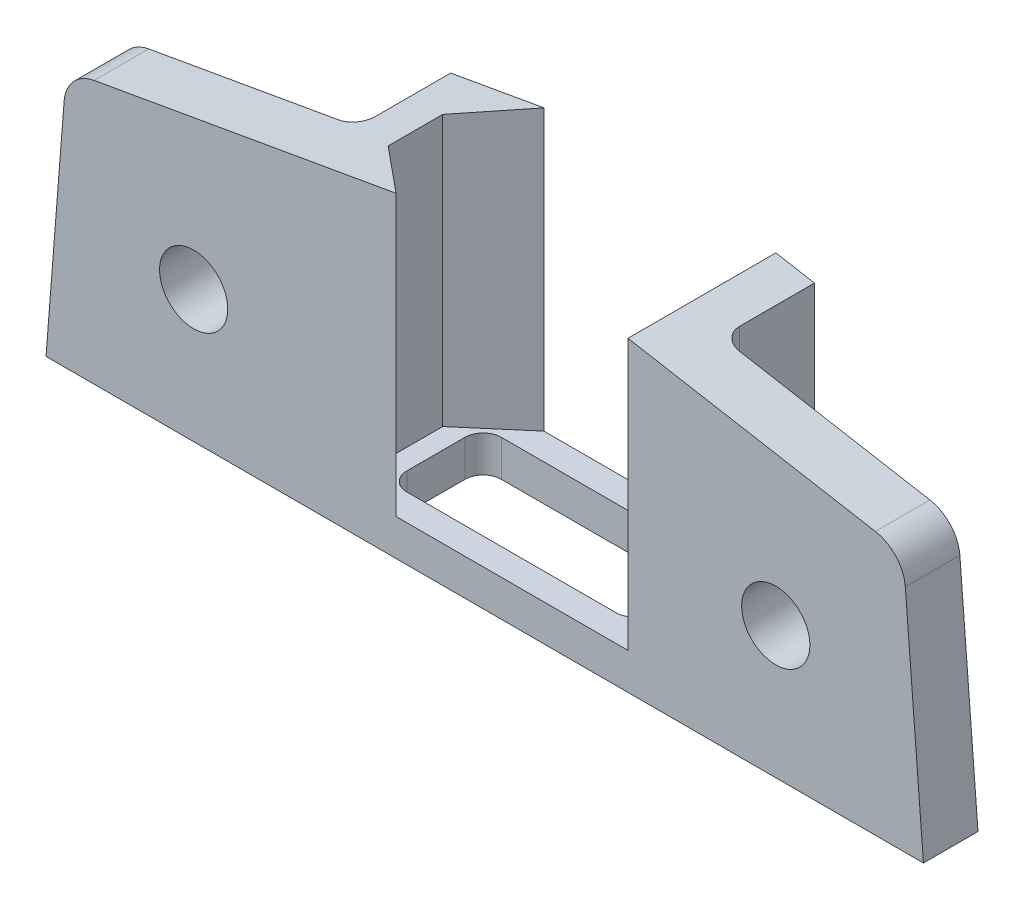
SolidWorks part; units mm, degrees
ref_plane "Front Plane" through (0, 0, 0) normal (0, 0, 1) x (1, 0, 0)
ref_plane "Top Plane" through (0, 0, 0) normal (0, 1, 0) x (1, 0, 0)
ref_plane "Right Plane" through (0, 0, 0) normal (1, 0, 0) x (0, 0, -1)
sketch "Sketch1" plane through (0, 0, 0) normal (0, 0, 1) x (1, 0, 0)
  line L0 (-24.457, 69.4319) -> (24.457, 69.4319)
  line L18 (24.457, 69.4319) -> (23.1215, 86.4007)
  line L19 (21.475, 88.2134) -> (0, 92)
  line L20 (0, 92) -> (-21.475, 88.2134)
  line L21 (-23.1215, 86.4007) -> (-24.457, 69.4319)
  line L22 (-24.5714, 68.9048) -> (-33.6515, 43.9576)
  line L23 (-33.4302, 42.1552) -> (-25.3419, 30.1639)
  line L24 (-25, 29.0455) -> (-25, -29.0455)
  line L25 (-25.3419, -30.1639) -> (-33.4302, -42.1552)
  line L26 (-33.6515, -43.9576) -> (-24.5714, -68.9048)
  line L27 (-24.457, -69.4319) -> (-23.1215, -86.4007)
  line L28 (-21.475, -88.2134) -> (0, -92)
  line L29 (0, -92) -> (21.475, -88.2134)
  line L30 (23.1215, -86.4007) -> (24.457, -69.4319)
  line L31 (24.5714, -68.9048) -> (33.6515, -43.9576)
  line L32 (33.4302, -42.1552) -> (25.3419, -30.1639)
  line L33 (25, -29.0455) -> (25, 29.0455)
  line L34 (25.3419, 30.1639) -> (33.4302, 42.1552)
  line L35 (33.6515, 43.9576) -> (24.5714, 68.9048)
  line L36 (24.457, 69.4319) -> (23.1215, 86.4007)
  line L37 (21.475, 88.2134) -> (0, 92)
  line L38 (0, 92) -> (-21.475, 88.2134)
  line L39 (-23.1215, 86.4007) -> (-24.457, 69.4319)
  circle A0 centre (-16, 81) radius 1.5 construction
  circle A1 centre (-16, 81) radius 1.5
  circle A2 centre (16, 81) radius 1.5 construction
  circle A3 centre (16, 81) radius 1.5
  arc A16 (24.457, 69.4319) -> (24.5714, 68.9048) centre (26.4508, 69.5889) ccw
  arc A17 (23.1215, 86.4007) -> (21.475, 88.2134) centre (21.1277, 86.2438) ccw
  arc A18 (-21.475, 88.2134) -> (-23.1215, 86.4007) centre (-21.1277, 86.2438) ccw
  arc A19 (-24.5714, 68.9048) -> (-24.457, 69.4319) centre (-26.4508, 69.5889) ccw
  arc A20 (-33.6515, 43.9576) -> (-33.4302, 42.1552) centre (-31.7721, 43.2736) ccw
  arc A21 (-25, 29.0455) -> (-25.3419, 30.1639) centre (-27, 29.0455) ccw
  arc A22 (-25.3419, -30.1639) -> (-25, -29.0455) centre (-27, -29.0455) ccw
  arc A23 (-33.4302, -42.1552) -> (-33.6515, -43.9576) centre (-31.7721, -43.2736) ccw
  arc A24 (-24.457, -69.4319) -> (-24.5714, -68.9048) centre (-26.4508, -69.5889) ccw
  arc A25 (-23.1215, -86.4007) -> (-21.475, -88.2134) centre (-21.1277, -86.2438) ccw
  arc A26 (21.475, -88.2134) -> (23.1215, -86.4007) centre (21.1277, -86.2438) ccw
  arc A27 (24.5714, -68.9048) -> (24.457, -69.4319) centre (26.4508, -69.5889) ccw
  arc A28 (33.6515, -43.9576) -> (33.4302, -42.1552) centre (31.7721, -43.2736) ccw
  arc A29 (25, -29.0455) -> (25.3419, -30.1639) centre (27, -29.0455) ccw
  arc A30 (25.3419, 30.1639) -> (25, 29.0455) centre (27, 29.0455) ccw
  arc A31 (33.4302, 42.1552) -> (33.6515, 43.9576) centre (31.7721, 43.2736) ccw
  arc A33 (23.1215, 86.4007) -> (21.475, 88.2134) centre (21.1277, 86.2438) ccw
  arc A34 (-21.475, 88.2134) -> (-23.1215, 86.4007) centre (-21.1277, 86.2438) ccw
  dimension "D1" = 0
extrude "Boss-Extrude1" add sketch "Sketch1" along normal blind 8.13
ref_plane "Plane1" through (0, 92, 0) normal (0, 1, 0) x (1, 0, 0)
sketch "Sketch2" plane through (0, 92, 0) normal (0, 1, 0) x (1, 0, 0)
  line L0 (0, -4.065) -> (24.457, -4.065) construction
  line L1 (0, -8.13) -> (0, 0) construction
  line L2 (24.457, -8.13) -> (24.457, 0) construction
  line L3 (21.475, -8.13) -> (0, -8.13) construction
  line L4 (-7.875, 0) -> (7.875, 0)
  line L5 (-7.875, 0) -> (-7.875, -8.13)
  line L6 (-7.875, -8.13) -> (7.875, -8.13)
  line L7 (7.875, 0) -> (7.875, -8.13)
  line L8 (-7.875, 0) -> (7.875, -8.13) construction
  line L9 (-7.875, -8.13) -> (7.875, 0) construction
  line L12 (-7.875, -2.565) -> (-4.875, 0)
  line L13 (-7.875, -5.565) -> (-4.875, -8.13)
  dimension "D1" = 15.75
  dimension "D4" = 12.75
  dimension "D5" = 3
extrude "Cut-Extrude1" cut sketch "Sketch2" against normal blind 16.25 contours L7 L4 L5 L6 region at (0.4396, 92, 4.065)
sketch "Sketch3" plane through (0, 75.75, 0) normal (0, 1, 0) x (1, 0, 0)
  line L0 (0, 0) -> (0, -8.13) construction
  line L1 (-4.875, -8.13) -> (7.875, -8.13) construction
  line L2 (0, -4.065) -> (24.457, -4.065) construction
  line L3 (24.457, -8.13) -> (24.457, 0) construction
  line L5 (-6.75, -1.465) -> (6.75, -1.465)
  line L6 (-6.75, -1.465) -> (-6.75, -6.665)
  line L7 (-6.75, -6.665) -> (6.75, -6.665)
  line L8 (6.75, -1.465) -> (6.75, -6.665)
  line L9 (-6.75, -1.465) -> (6.75, -6.665) construction
  line L10 (-6.75, -6.665) -> (6.75, -1.465) construction
  dimension "D1" = 13.5
  dimension "D2" = 5.2
extrude "Cut-Extrude2" cut sketch "Sketch3" against normal up to next
sketch "Sketch4" plane through (0, 0, 0) normal (0, 0, -1) x (-1, 0, 0)
  line L0 (-10, 90.2367) -> (-10, 69.4319)
  line L1 (0, 69.4319) -> (0, 91.1404) construction
  line L2 (10, 90.2367) -> (10, 69.4319)
  line L8 (21.475, 88.2134) -> (4.875, 91.1404)
  line L9 (4.875, 91.1404) -> (4.875, 75.75)
  line L10 (4.875, 75.75) -> (-7.875, 75.75)
  line L11 (4.875, 91.1404) -> (4.875, 75.75)
  line L12 (-7.875, 90.6114) -> (-21.475, 88.2134)
  line L13 (-23.1215, 86.4007) -> (-24.457, 69.4319)
  line L14 (-24.457, 69.4319) -> (24.457, 69.4319)
  line L15 (24.457, 69.4319) -> (23.1215, 86.4007)
  line L16 (21.475, 88.2134) -> (4.875, 91.1404)
  line L17 (-7.875, 75.75) -> (-7.875, 90.6114)
  line L18 (4.875, 75.75) -> (-7.875, 75.75)
  line L19 (-7.875, 75.75) -> (-7.875, 90.6114)
  line L20 (-7.875, 90.6114) -> (-21.475, 88.2134)
  line L21 (-23.1215, 86.4007) -> (-24.457, 69.4319)
  line L22 (-24.457, 69.4319) -> (24.457, 69.4319)
  line L23 (24.457, 69.4319) -> (23.1215, 86.4007)
  arc A2 (-21.475, 88.2134) -> (-23.1215, 86.4007) centre (-21.1277, 86.2438) ccw
  arc A3 (23.1215, 86.4007) -> (21.475, 88.2134) centre (21.1277, 86.2438) ccw
  arc A4 (-21.475, 88.2134) -> (-23.1215, 86.4007) centre (-21.1277, 86.2438) ccw
  arc A5 (23.1215, 86.4007) -> (21.475, 88.2134) centre (21.1277, 86.2438) ccw
  line M11 (21.475, 88.2134) -> (4.875, 91.1404)
  line M15 (-7.875, 90.6114) -> (-21.475, 88.2134)
  arc M16 (-21.475, 88.2134) -> (-23.1215, 86.4007) centre (-21.1277, 86.2438) ccw
  line M17 (-23.1215, 86.4007) -> (-24.457, 69.4319)
  line M18 (-24.457, 69.4319) -> (24.457, 69.4319)
  line M19 (24.457, 69.4319) -> (23.1215, 86.4007)
  arc M20 (23.1215, 86.4007) -> (21.475, 88.2134) centre (21.1277, 86.2438) ccw
  circle M21 centre (16, 81) radius 1.5
  circle M22 centre (-16, 81) radius 1.5
  dimension "D2" = 10
  dimension "D1" = 0
extrude "Cut-Extrude3" cut sketch "Sketch4" against normal offset from surface (5.13 mm away) 3 contours L0 M15 M16 M17 M18 M22 | L2 M11 M18 M19 M20 M21 region at (16.7394, 79.0217, 0) region at (-16.7394, 79.0217, 0) up to face at (17.5, 81, 8.13)
sketch "Sketch5" plane through (0, 0, 0) normal (0, 0, -1) x (-1, 0, 0)
  line L1 (4.875, 75.75) -> (-7.875, 75.75) construction
  line L2 (-24.457, 69.4319) -> (24.457, 69.4319)
  line L3 (-24.457, 69.4319) -> (-24.457, 73.75)
  line L4 (-24.457, 73.75) -> (24.457, 73.75)
  line L6 (24.457, 69.4319) -> (24.457, 73.75)
  dimension "D1" = 2
extrude "Cut-Extrude4" cut sketch "Sketch5" against normal up to next
fillet "Fillet1" radius 1 6 edges at (-6.75, 74.75, 1.465) (6.75, 74.75, 1.465) (6.75, 74.75, 6.665) (-6.75, 74.75, 6.665) (-10, 81.9934, 5.13) (10, 81.9934, 5.13)
sketch "Sketch8" plane through (0, 0, 5.13) normal (0, 0, -1) x (-1, 0, 0)
  circle A0 centre (16, 81) radius 1.875
  circle A1 centre (-16, 81) radius 1.875
  dimension "D1" = 3.75
extrude "Cut-Extrude6" cut sketch "Sketch8" against normal up to next
